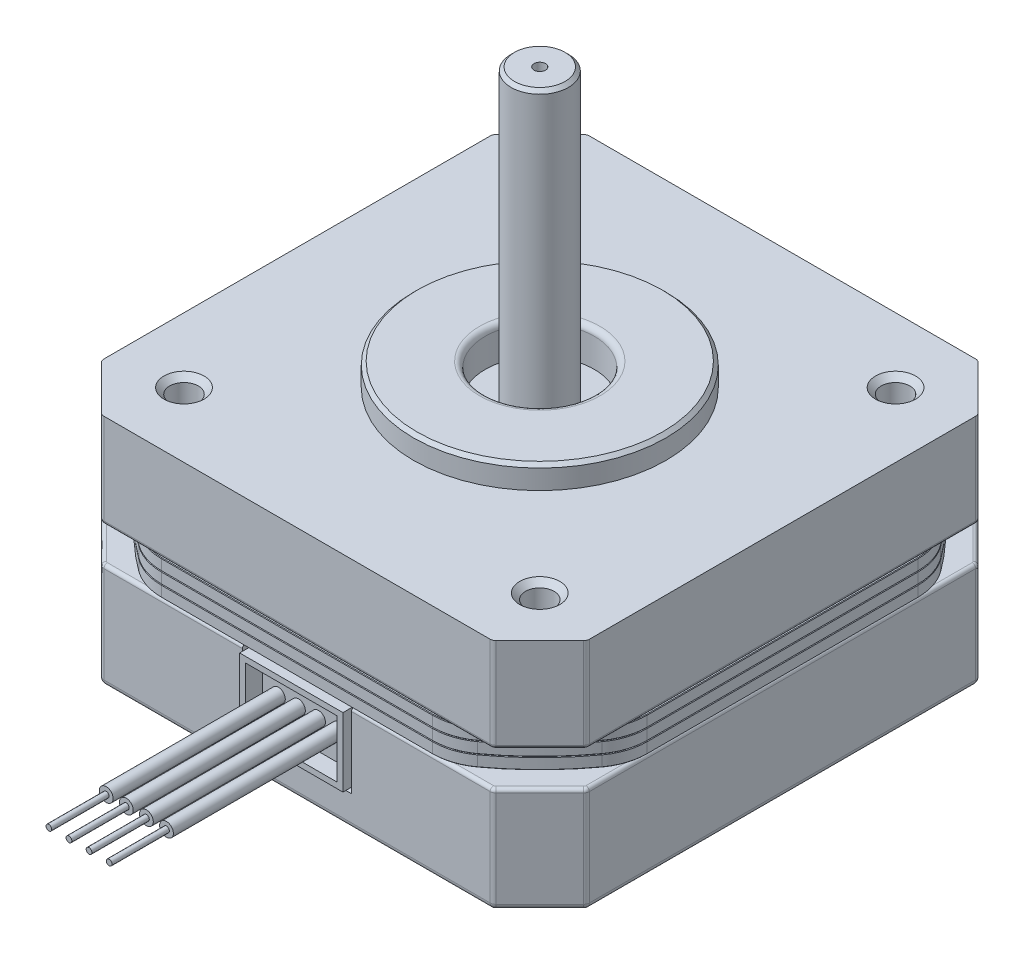
SolidWorks part; units mm, degrees
note: The reader was unsure of these and kept them because the rebuilt part matched: shared geometry of "Эскиз1<3>", "Эскиз12<2>".
ref_plane "Спереди" through (0, 0, 0) normal (0, 0, 1) x (1, 0, 0)
ref_plane "Сверху" through (0, 0, 0) normal (0, 1, 0) x (1, 0, 0)
ref_plane "Справа" through (0, 0, 0) normal (1, 0, 0) x (0, 0, -1)
sketch "Эскиз1" plane through (0, 0, 0) normal (0, 1, 0) x (1, 0, 0)
  line L0 (-21.15, 17.0338) -> (-17.0338, 21.15)
  line L1 (-21.15, 21.15) -> (21.15, 21.15)
  line L2 (-21.15, 21.15) -> (-21.15, -21.15)
  line L3 (-21.15, -21.15) -> (21.15, -21.15)
  line L4 (21.15, 21.15) -> (21.15, -21.15)
  line L5 (-21.15, 21.15) -> (21.15, -21.15) construction
  line L6 (-21.15, -21.15) -> (21.15, 21.15) construction
  line L7 (-17.0338, 21.15) -> (17.0338, 21.15)
  line L8 (17.0338, 21.15) -> (21.15, 17.0338)
  line L9 (21.15, 17.0338) -> (21.15, -17.0338)
  line L10 (21.15, -17.0338) -> (17.0338, -21.15)
  line L11 (17.0338, -21.15) -> (-17.0338, -21.15)
  line L12 (-17.0338, -21.15) -> (-21.15, -17.0338)
  point P0 (0, 0)
  dimension "D1" = 42.3
  dimension "D2" = 54
extrude "Бобышка-Вытянуть1" add sketch "Эскиз1" along normal blind 9.2 contours L12 L3 L10 L4 L8 L1 L0 L2
extrude "Бобышка-Вытянуть2" add sketch "Эскиз1<3>" against normal blind 8.2 from offset 20.4 separate body contours L12 L3 L10 L4 L8 L1 L0 L2
sketch "Эскиз1<3>" plane through (0, 0, 0) normal (0, 1, 0) x (1, 0, 0) same geometry as "Эскиз1"
sketch "Эскиз2" plane through (0, 9.2, 0) normal (0, 1, 0) x (1, 0, 0)
  line L16 (-21.15, -17.0338) -> (-17.0338, -21.15)
  line L17 (-17.0338, -21.15) -> (17.0338, -21.15)
  line L18 (17.0338, -21.15) -> (21.15, -17.0338)
  line L19 (21.15, -17.0338) -> (21.15, 17.0338)
  line L20 (21.15, 17.0338) -> (17.0338, 21.15)
  line L21 (17.0338, 21.15) -> (-17.0338, 21.15)
  line L22 (-17.0338, 21.15) -> (-21.15, 17.0338)
  line L23 (-21.15, 17.0338) -> (-21.15, -17.0338)
  line L25 (-11.7974, -21.15) -> (11.7974, -21.15)
  line L27 (21.15, -11.7974) -> (21.15, 11.7974)
  line L29 (11.7974, 21.15) -> (-11.7974, 21.15)
  line L31 (-21.15, 11.7974) -> (-21.15, -11.7974)
  arc A0 (-20.1875, -14.7467) -> (-14.7467, -20.1875) centre (0, 0) ccw
  arc A1 (-14.7467, 20.1875) -> (-20.1875, 14.7467) centre (0, 0) ccw
  arc A2 (20.1875, 14.7467) -> (14.7467, 20.1875) centre (0, 0) ccw
  arc A3 (14.7467, -20.1875) -> (20.1875, -14.7467) centre (0, 0) ccw
  arc A4 (14.7467, 20.1875) -> (11.7974, 21.15) centre (11.7974, 16.15) ccw
  arc A5 (21.15, 11.7974) -> (20.1875, 14.7467) centre (16.15, 11.7974) ccw
  arc A6 (20.1875, -14.7467) -> (21.15, -11.7974) centre (16.15, -11.7974) ccw
  arc A7 (11.7974, -21.15) -> (14.7467, -20.1875) centre (11.7974, -16.15) ccw
  arc A8 (-14.7467, -20.1875) -> (-11.7974, -21.15) centre (-11.7974, -16.15) ccw
  arc A9 (-20.1875, -14.7467) -> (-21.15, -11.7974) centre (-16.15, -11.7974) cw
  arc A10 (-20.1875, 14.7467) -> (-21.15, 11.7974) centre (-16.15, 11.7974) ccw
  arc A11 (-11.7974, 21.15) -> (-14.7467, 20.1875) centre (-11.7974, 16.15) ccw
  point P22 (21.15, 13.3296)
  point P27 (13.3296, -21.15)
  point P36 (-13.3296, 21.15)
  dimension "D1" = 50
  dimension "D3" = 5
  dimension "D2" = 0
extrude "Бобышка-Вытянуть3" add sketch "Эскиз2" along normal blind 1 separate body
pattern_linear "Линейный массив1" count 3 spacing 1 along (0, 1, 0) of bodies 105
sketch "Эскиз3" plane through (0, 0, 0) normal (0, -1, 0) x (1, 0, 0)
  circle A0 centre (0, 0) radius 4.75
  dimension "D1" = 9.5
extrude "Вырез-Вытянуть1" cut sketch "Эскиз3" against normal blind 3
sketch "Эскиз4" plane through (0, 3, 0) normal (0, -1, 0) x (1, 0, 0)
  circle A0 centre (0, 0) radius 2.5
  circle A1 centre (0, 0) radius 4.75
  dimension "D1" = 5
extrude "Вырез-Вытянуть2" cut sketch "Эскиз4" against normal blind 0.5
sketch "Эскиз5" plane through (0, 3, 0) normal (0, -1, 0) x (1, 0, 0)
  circle A0 centre (0, 0) radius 0.5
  dimension "D1" = 1
extrude "Вырез-Вытянуть3" cut sketch "Эскиз5" against normal blind 0.5
chamfer "Фаска1" distance 0.3 angle 45 1 edges at (0, 3, -2.5)
fillet "Скругление1" radius 0.5 17 edges at (0, 0, 21.15) (19.0919, 0, 19.0919) (21.15, 0, 0) (19.0919, 0, -19.0919) (0, 0, -21.15) (-19.0919, 0, -19.0919) (-21.15, 0, 0) (-19.0919, 0, 19.0919) (0, 0, -4.75) (21.15, 4.6, 17.0338) (17.0338, 4.6, 21.15) (-17.0338, 4.6, 21.15) (-21.15, 4.6, 17.0338) (-21.15, 4.6, -17.0338) (-17.0338, 4.6, -21.15) (17.0338, 4.6, -21.15) (21.15, 4.6, -17.0338)
fillet "Скругление2" radius 0.5 8 edges at (21.15, 16.3, 17.0338) (17.0338, 16.3, 21.15) (-17.0338, 16.3, 21.15) (-21.15, 16.3, 17.0338) (-21.15, 16.3, -17.0338) (-17.0338, 16.3, -21.15) (17.0338, 16.3, -21.15) (21.15, 16.3, -17.0338)
sketch "Эскиз6" plane through (0, 20.4, 0) normal (0, 1, 0) x (1, 0, 0)
  circle A0 centre (0, 0) radius 11
  circle A1 centre (0, 0) radius 4.75
  dimension "D1" = 22
  dimension "D2" = 9.5
extrude "Бобышка-Вытянуть4" add sketch "Эскиз6" along normal blind 2
sketch "Эскиз7" plane through (0, 20.4, 0) normal (0, 1, 0) x (1, 0, 0)
  circle A2 centre (0, 0) radius 4.75
  circle A3 centre (0, 0) radius 4.75
  dimension "D1" = 0
extrude "Вырез-Вытянуть4" cut sketch "Эскиз7" against normal blind 1
chamfer "Фаска2" distance 0.3 angle 45 1 edges at (0, 22.4, 11)
fillet "Скругление3" radius 0.5 1 edges at (0, 22.4, 4.75)
sketch "Эскиз8" plane through (0, 19.4, 0) normal (0, 1, 0) x (1, 0, 0)
  circle A0 centre (0, 0) radius 2.5
  dimension "D1" = 5
extrude "Бобышка-Вытянуть5" add sketch "Эскиз8" along normal blind 25.2
chamfer "Фаска4" distance 0.3 angle 45 1 edges at (0, 44.6, 2.5)
sketch "Эскиз9" plane through (0, 44.6, 0) normal (0, 1, 0) x (1, 0, 0)
  circle A0 centre (0, 0) radius 0.5
  dimension "D1" = 1
extrude "Вырез-Вытянуть5" cut sketch "Эскиз9" against normal blind 1
sketch "Эскиз10" plane through (0, 0, 21.15) normal (0, 0, 1) x (1, 0, 0)
  line L0 (0, 0) -> (0, 9.2) construction
  line L1 (-11.7974, 9.2) -> (11.7974, 9.2) construction
  line L2 (-16.8267, 9.2) -> (16.8267, 9.2) construction
  line L3 (-4.75, 2.7) -> (4.75, 2.7)
  line L4 (-4.75, 2.7) -> (-4.75, 9.2)
  line L5 (-4.75, 9.2) -> (4.75, 9.2)
  line L6 (4.75, 2.7) -> (4.75, 9.2)
  line L7 (-4.75, 2.7) -> (4.75, 9.2) construction
  line L8 (-4.75, 9.2) -> (4.75, 2.7) construction
  point P5 (0, 5.95)
  dimension "D1" = 9.5
  dimension "D2" = 6.5
extrude "Вырез-Вытянуть6" cut sketch "Эскиз10" against normal blind 1
sketch "Эскиз11" plane through (0, 0, 20.15) normal (0, 0, 1) x (1, 0, 0)
  line L8 (4.5, 2.95) -> (4.5, 8.95)
  line L9 (4.5, 8.95) -> (-4.5, 8.95)
  line L10 (-4.5, 8.95) -> (-4.5, 2.95)
  line L11 (-4.5, 2.95) -> (4.5, 2.95)
  line L12 (4.5, 2.95) -> (4.5, 8.95)
  line L13 (4.5, 8.95) -> (-4.5, 8.95)
  line L14 (-4.5, 8.95) -> (-4.5, 2.95)
  line L15 (-4.5, 2.95) -> (4.5, 2.95)
  line L20 (4, 3.45) -> (4, 8.45)
  line L21 (4, 8.45) -> (-4, 8.45)
  line L22 (-4, 8.45) -> (-4, 3.45)
  line L23 (-4, 3.45) -> (4, 3.45)
  line L24 (4, 3.45) -> (4, 8.45)
  line L25 (4, 8.45) -> (-4, 8.45)
  line L26 (-4, 8.45) -> (-4, 3.45)
  line L27 (-4, 3.45) -> (4, 3.45)
  dimension "D1" = 0.25
  dimension "D2" = 0.75
extrude "Бобышка-Вытянуть6" add sketch "Эскиз11" along normal blind 1.5 separate body
sketch "Эскиз12" plane through (0, 0, 20.15) normal (0, 0, 1) x (1, 0, 0)
  line L0 (-4, 5.95) -> (4, 5.95) construction
  line L1 (-4, 8.45) -> (-4, 3.45) construction
  line L2 (4, 3.45) -> (4, 8.45) construction
  line L3 (-2.625, 5.95) -> (-2.625, 4.3362) construction
  line L4 (-2.625, 4.3362) -> (-0.875, 4.3362) construction
  line L5 (-0.875, 4.3362) -> (-0.875, 5.95) construction
  line L6 (-0.875, 5.95) -> (-0.875, 4.3362) construction
  line L7 (-0.875, 4.3362) -> (0.875, 4.3362) construction
  line L8 (0.875, 4.3362) -> (0.875, 5.95) construction
  line L9 (0.875, 5.95) -> (0.875, 4.3362) construction
  line L10 (0.875, 4.3362) -> (2.625, 4.3362) construction
  line L11 (2.625, 4.3362) -> (2.625, 5.95) construction
  line L12 (0, 5.95) -> (0, 4.3362) construction
  circle A0 centre (-2.625, 5.95) radius 0.6
  circle A1 centre (-0.875, 5.95) radius 0.6
  circle A2 centre (0.875, 5.95) radius 0.6
  circle A3 centre (2.625, 5.95) radius 0.6
  circle A4 centre (-2.625, 5.95) radius 0.25
  circle A5 centre (-0.875, 5.95) radius 0.25
  circle A6 centre (0.875, 5.95) radius 0.25
  circle A7 centre (2.625, 5.95) radius 0.25
  dimension "D1" = 1.2
  dimension "D2" = 0.5
  dimension "D3" = 1.75
extrude "Бобышка-Вытянуть7" add sketch "Эскиз12" along normal blind 15 separate body
extrude "Бобышка-Вытянуть8" add sketch "Эскиз12<2>" along normal blind 20 separate body contours A4 | A5 | A6 | A7
sketch "Эскиз12<2>" plane through (0, 0, 20.15) normal (0, 0, 1) x (1, 0, 0) same geometry as "Эскиз12"
chamfer "Фаска32" distance 0.05 angle 45 32 edges at (-17.6777, 12.2, -17.6777) (-20.9033, 12.2, -13.3486) (-13.3486, 12.2, -20.9033) (-21.15, 12.2, 0) (0, 12.2, -21.15) (-20.9033, 12.2, 13.3486) (13.3486, 12.2, -20.9033) (-17.6777, 12.2, 17.6777) (17.6777, 12.2, -17.6777) (-13.3486, 12.2, 20.9033) (20.9033, 12.2, -13.3486) (0, 12.2, 21.15) (21.15, 12.2, 0) (13.3486, 12.2, 20.9033) (20.9033, 12.2, 13.3486) (17.6777, 12.2, 17.6777) (-17.6777, 11.2, -17.6777) (-20.9033, 11.2, -13.3486) (-13.3486, 11.2, -20.9033) (-21.15, 11.2, 0) (0, 11.2, -21.15) (-20.9033, 11.2, 13.3486) (13.3486, 11.2, -20.9033) (-17.6777, 11.2, 17.6777) (17.6777, 11.2, -17.6777) (-13.3486, 11.2, 20.9033) (20.9033, 11.2, -13.3486) (0, 11.2, 21.15) (21.15, 11.2, 0) (13.3486, 11.2, 20.9033) (20.9033, 11.2, 13.3486) (17.6777, 11.2, 17.6777)
chamfer "Фаска33" distance 0.05 angle 45 32 edges at (-17.6777, 11.2, -17.6777) (-20.9033, 11.2, -13.3486) (-13.3486, 11.2, -20.9033) (-21.15, 11.2, 0) (0, 11.2, -21.15) (-20.9033, 11.2, 13.3486) (13.3486, 11.2, -20.9033) (-17.6777, 11.2, 17.6777) (17.6777, 11.2, -17.6777) (-13.3486, 11.2, 20.9033) (20.9033, 11.2, -13.3486) (0, 11.2, 21.15) (21.15, 11.2, 0) (13.3486, 11.2, 20.9033) (20.9033, 11.2, 13.3486) (17.6777, 11.2, 17.6777) (-17.6777, 10.2, -17.6777) (-20.9033, 10.2, -13.3486) (-13.3486, 10.2, -20.9033) (-21.15, 10.2, 0) (0, 10.2, -21.15) (-20.9033, 10.2, 13.3486) (13.3486, 10.2, -20.9033) (-17.6777, 10.2, 17.6777) (17.6777, 10.2, -17.6777) (-13.3486, 10.2, 20.9033) (20.9033, 10.2, -13.3486) (0, 10.2, 21.15) (21.15, 10.2, 0) (13.3486, 10.2, 20.9033) (20.9033, 10.2, 13.3486) (17.6777, 10.2, 17.6777)
chamfer "Фаска34" distance 0.05 angle 45 32 edges at (-17.6777, 10.2, -17.6777) (-20.9033, 10.2, -13.3486) (-13.3486, 10.2, -20.9033) (-21.15, 10.2, 0) (0, 10.2, -21.15) (-20.9033, 10.2, 13.3486) (13.3486, 10.2, -20.9033) (-17.6777, 10.2, 17.6777) (17.6777, 10.2, -17.6777) (-13.3486, 10.2, 20.9033) (20.9033, 10.2, -13.3486) (0, 10.2, 21.15) (21.15, 10.2, 0) (13.3486, 10.2, 20.9033) (20.9033, 10.2, 13.3486) (17.6777, 10.2, 17.6777) (-17.6777, 9.2, -17.6777) (-20.9033, 9.2, -13.3486) (-13.3486, 9.2, -20.9033) (-21.15, 9.2, 0) (0, 9.2, -21.15) (-20.9033, 9.2, 13.3486) (13.3486, 9.2, -20.9033) (-17.6777, 9.2, 17.6777) (17.6777, 9.2, -17.6777) (-13.3486, 9.2, 20.9033) (20.9033, 9.2, -13.3486) (0, 9.2, 21.15) (21.15, 9.2, 0) (13.3486, 9.2, 20.9033) (20.9033, 9.2, 13.3486) (17.6777, 9.2, 17.6777)
sketch "Эскиз16" plane through (0, 20.4, 0) normal (0, 1, 0) x (1, 0, 0)
  line L1 (-15.5, 15.5) -> (15.5, 15.5) construction
  line L2 (-15.5, 15.5) -> (-15.5, -15.5) construction
  line L3 (-15.5, -15.5) -> (15.5, -15.5) construction
  line L4 (15.5, 15.5) -> (15.5, -15.5) construction
  line L5 (-15.5, 15.5) -> (15.5, -15.5) construction
  line L6 (-15.5, -15.5) -> (15.5, 15.5) construction
  circle A0 centre (-15.5, 15.5) radius 1.25
  circle A1 centre (15.5, 15.5) radius 1.25
  circle A2 centre (15.5, -15.5) radius 1.25
  circle A3 centre (-15.5, -15.5) radius 1.25
  point P0 (0, 0)
  dimension "D1" = 2.5
  dimension "D2" = 31
extrude "Вырез-Вытянуть9" cut sketch "Эскиз16" against normal blind 7
chamfer "Фаска35" distance 0.5 angle 45 4 edges at (-15.5, 20.4, 16.75) (15.5, 20.4, 16.75) (15.5, 20.4, -14.25) (-15.5, 20.4, -14.25)
fillet "Скругление4" radius 0.3 17 edges at (-10.7883, 9.2, 21.15) (-17.018, 9.2, 21.1119) (-19.0919, 9.2, 19.0919) (-21.1119, 9.2, 17.018) (-21.15, 9.2, 0) (-21.1119, 9.2, -17.018) (-19.0919, 9.2, -19.0919) (-17.018, 9.2, -21.1119) (0, 9.2, -21.15) (17.018, 9.2, -21.1119) (19.0919, 9.2, -19.0919) (21.1119, 9.2, -17.018) (21.15, 9.2, 0) (21.1119, 9.2, 17.018) (10.7883, 9.2, 21.15) (17.018, 9.2, 21.1119) (19.0919, 9.2, 19.0919)
fillet "Скругление5" radius 0.3 16 edges at (21.1119, 12.2, 17.018) (21.15, 12.2, 0) (21.1119, 12.2, -17.018) (19.0919, 12.2, -19.0919) (17.018, 12.2, -21.1119) (0, 12.2, -21.15) (-17.018, 12.2, -21.1119) (-19.0919, 12.2, -19.0919) (-21.1119, 12.2, -17.018) (-21.15, 12.2, 0) (-21.1119, 12.2, 17.018) (-19.0919, 12.2, 19.0919) (-17.018, 12.2, 21.1119) (0, 12.2, 21.15) (17.018, 12.2, 21.1119) (19.0919, 12.2, 19.0919)
